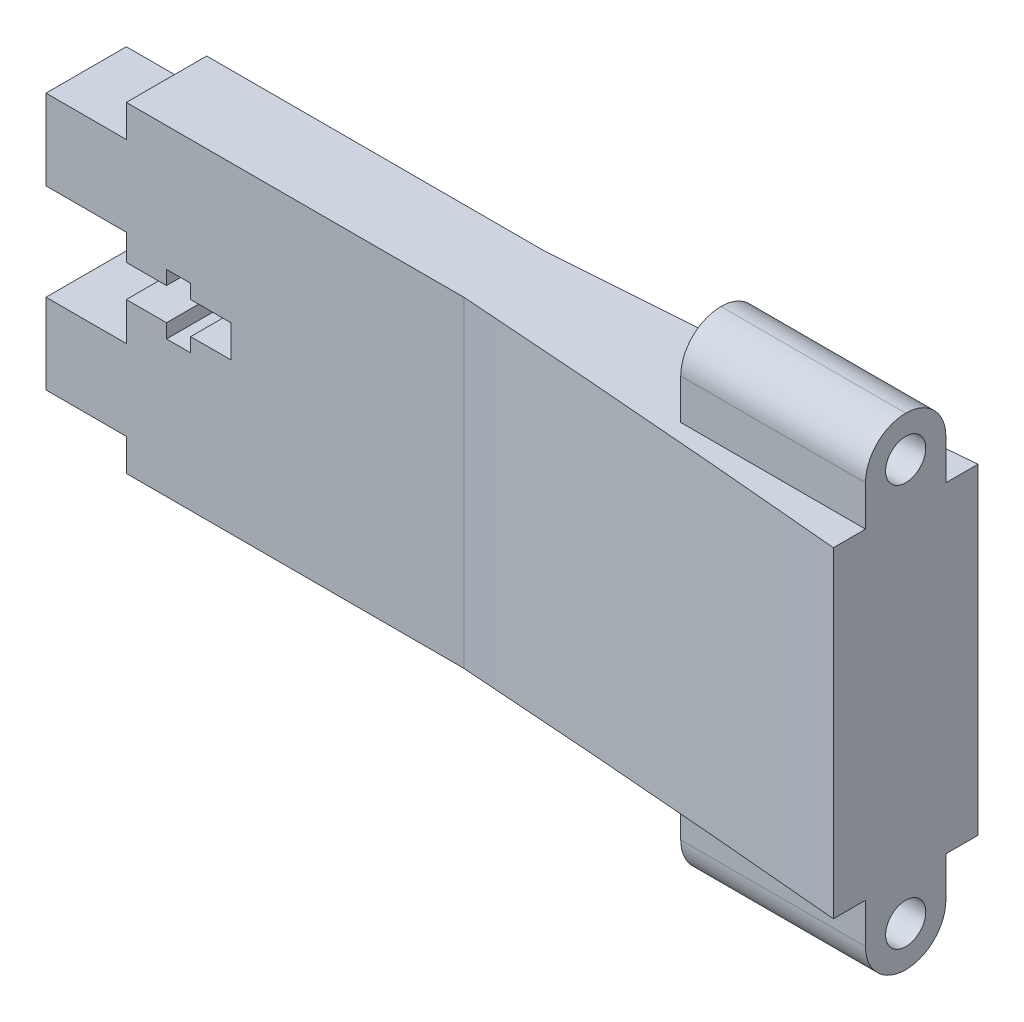
SolidWorks part; units mm, degrees
ref_plane "Front Plane" through (0, 0, 0) normal (0, 0, 1) x (1, 0, 0)
ref_plane "Top Plane" through (0, 0, 0) normal (0, 1, 0) x (1, 0, 0)
ref_plane "Right Plane" through (0, 0, 0) normal (1, 0, 0) x (0, 0, -1)
sketch "Sketch1" plane through (0, 0, 0) normal (0, 0, 1) x (1, 0, 0)
  line L5 (-38, 4.5) -> (-38, 2.75)
  line L6 (23, -20) -> (-46, -20)
  line L18 (0, 0) -> (0, -12.9172) construction
  line L42 (23, 20) -> (-46, 20)
  line L43 (-46, -20) -> (-46, -16)
  line L44 (46, -20) -> (-46, 20) construction
  line L45 (46, 20) -> (-46, -20) construction
  line L46 (-33, -1.25) -> (-38, -1.25)
  line L47 (-33, -1.25) -> (-33, 2.75)
  line L48 (-33, 2.75) -> (-38, 2.75)
  line L49 (-41, 4.5) -> (-41, 2.75)
  line L50 (-41, -3) -> (-38, -3)
  line L51 (-41, 4.5) -> (-38, 4.5)
  line L52 (-41, -1.25) -> (-46, -1.25)
  line L53 (-41, 2.75) -> (-46, 2.75)
  line L54 (-41, -1.25) -> (-41, -3)
  line L55 (-38, -1.25) -> (-38, -3)
  line L56 (0, 0) -> (-13.3376, 0) construction
  line L57 (-46, 2.75) -> (-46, 6)
  line L58 (-46, -16) -> (-56, -16)
  line L59 (-46, -6) -> (-56, -6)
  line L60 (-56, -16) -> (-56, -6)
  line L61 (-46, -6) -> (-46, -1.25)
  line L62 (-46, 16) -> (-56, 16)
  line L63 (-56, 16) -> (-56, 6)
  line L66 (-46, 6) -> (-56, 6)
  line L67 (-46, 16) -> (-46, 20)
  line L68 (46, -20) -> (46, -16)
  line L72 (46, -6) -> (46, -1.25)
  line L73 (46, -20) -> (46, -30)
  line L74 (46, -30) -> (23, -30)
  line L75 (23, -30) -> (23, -20)
  line L76 (46, 20) -> (46, 30)
  line L77 (46, 30) -> (23, 30)
  line L78 (23, 30) -> (23, 20)
  line L79 (46, 16) -> (46, 6)
  line L80 (46, -6) -> (46, -16)
  line L84 (46, 2.75) -> (46, 6)
  line L88 (46, 16) -> (46, 20)
  line L89 (46, 2.75) -> (46, -1.25)
  point P0 (0, 0)
  dimension "D15" = 23
  dimension "D1" = 40
  dimension "D2" = 92
  dimension "D3" = 18.75
  dimension "D4" = 22.75
  dimension "D5" = 13
  dimension "D6" = 5
  dimension "D7" = 3
  dimension "D8" = 7.5
  dimension "D9" = 1.75
  dimension "D10" = 4
  dimension "D11" = 10
  dimension "D12" = 10
  dimension "D13" = 23
  dimension "D14" = 10
  dimension "D16" = 10
  dimension "D17" = 0
  dimension "D18" = 0
extrude "Boss-Extrude1" add sketch "Sketch1" along normal mid plane 10 contours L42 L67 L62 L63 L66 L57 L53 L49 L51 L5 L48 L47 L46 L55 L50 L54 L52 L61 L59 L60 L58 L43 L6 region at (1.9027, -0.011, 0)
sketch "Sketch2" plane through (23, 0, 0) normal (-1, 0, 0) x (0, 0, 1)
  line L0 (5, -30) -> (-5, -30) construction
  line L1 (-5, -30) -> (-5, -20) construction
  circle A0 centre (0, -25) radius 2.5
  dimension "D2" = 5
  dimension "D1" = 5
  dimension "D3" = 5
extrude "Cut-Extrude1" cut sketch "Sketch2" against normal through all
sketch "Sketch3" plane through (23, 0, 0) normal (-1, 0, 0) x (0, 0, 1)
  line L0 (5, 30) -> (5, 20) construction
  line L1 (5, 30) -> (-5, 30) construction
  circle A0 centre (0, 25) radius 2.5
  dimension "D2" = 5
  dimension "D1" = 5
  dimension "D3" = 5
extrude "Cut-Extrude2" cut sketch "Sketch3" against normal through all
fillet "Fillet1" radius 5 4 edges at (34.5, -30, 5) (34.5, -30, -5) (34.5, 30, 5) (34.5, 30, -5)
sketch "Çizim2" plane through (0, 0, 0) normal (0, 1, 0) x (1, 0, 0)
  line L3 (46, 5) -> (-4, 5)
  line L4 (46, 5) -> (46, 9)
  spline S0 degree 2 poles (-4, 5) (21.0251, 6.6976) (46, 9) knots 0 0 0 1 1 1
  dimension "D1" = 5
  dimension "D2" = 50
  dimension "D3" = 4
  dimension "D4" = 46
  dimension "D5" = 2.86
  dimension "D6" = 12.8
extrude "Yükseklik-Ekstrüzyon1" add sketch "Çizim2" along normal mid plane 40
mirror "Mirror1" about plane through (0, 0, 0) normal (0, 0, 1) of "Yükseklik-Ekstrüzyon1"
